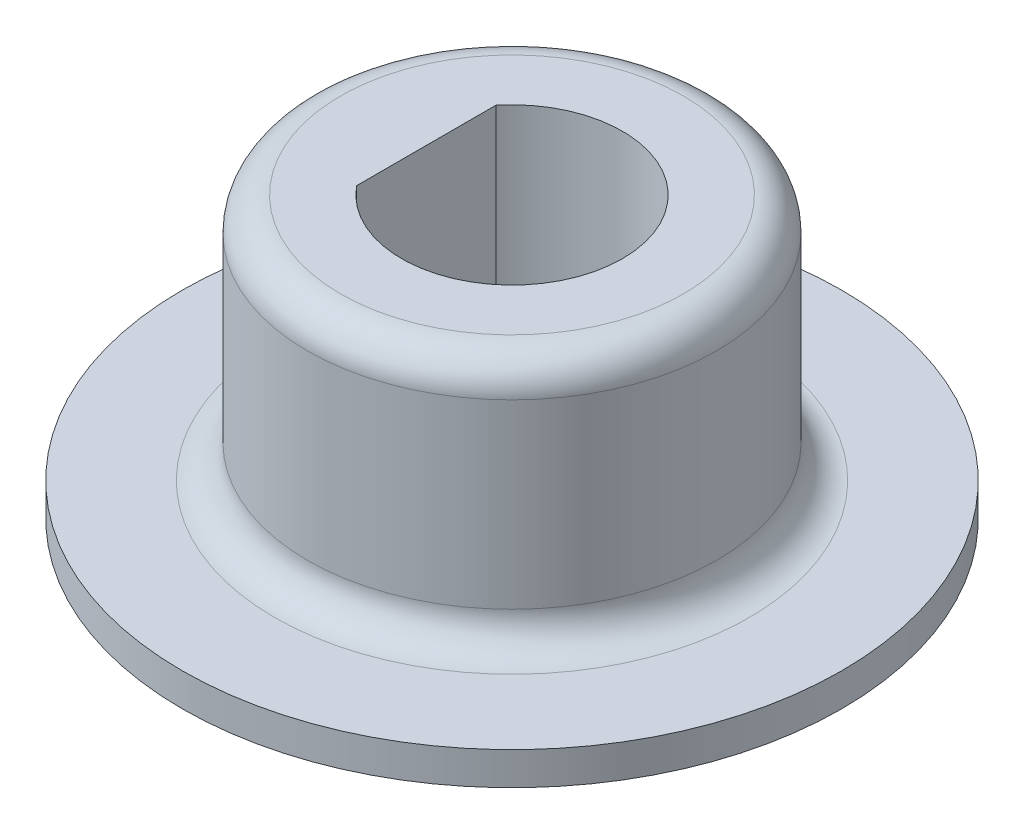
SolidWorks part; units mm, degrees
material "ABS"
ref_plane "Plan de face" through (0, 0, 0) normal (0, 0, 1) x (1, 0, 0)
ref_plane "Plan de dessus" through (0, 0, 0) normal (0, 1, 0) x (1, 0, 0)
ref_plane "Plan de droite" through (0, 0, 0) normal (1, 0, 0) x (0, 0, -1)
sketch "Sketch2" plane through (0, 0, 0) normal (0, 0, 1) x (1, 0, 0)
  line L0 (0, 0) -> (0, 8.5)
  line L1 (0, 8.5) -> (-6.2, 8.5)
  line L2 (-6.2, 8.5) -> (-6.2, 1)
  line L3 (-6.2, 1) -> (-10, 1)
  line L4 (-10, 1) -> (-10, 0)
  line L5 (-10, 0) -> (0, 0)
  dimension "D1" = 8.5
  dimension "D2" = 1
  dimension "D3" = 10
  dimension "D4" = 6.2
revolve "Revolve1" add sketch "Sketch2" angle 360 about L0
sketch "Sketch3" plane through (0, 8.5, 0) normal (0, 1, 0) x (1, 0, 0)
  line L0 (-2.6, 2.1125) -> (-2.6, -2.1125)
  arc A0 (-2.6, -2.1125) -> (-2.6, 2.1125) centre (0, 0) ccw
  dimension "D1" = 3.35
  dimension "D2" = 2.6
extrude "Cut-Extrude1" cut sketch "Sketch3" against normal blind 10
fillet "Fillet1" radius 1 2 edges at (0, 1, -6.2) (0, 8.5, -6.2)
